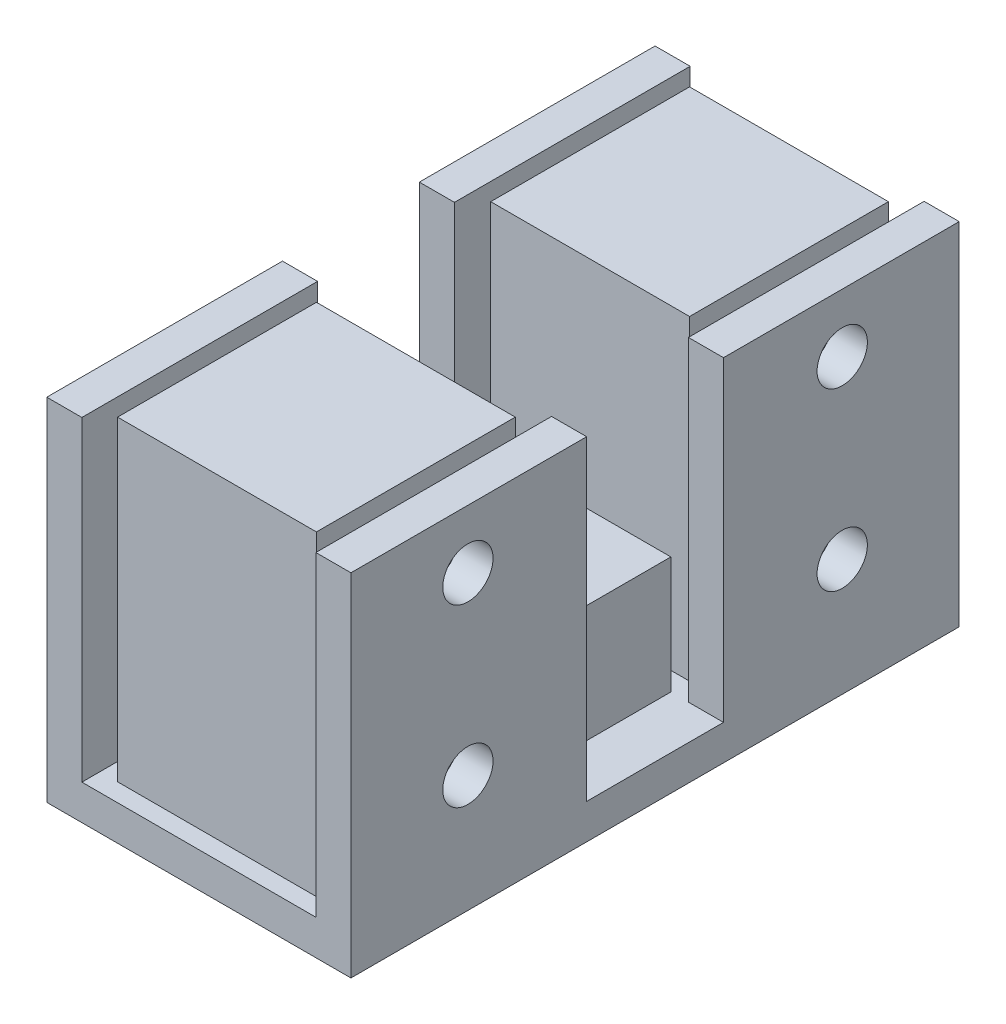
SolidWorks part; units mm, degrees
ref_plane "Front Plane" through (0, 0, 0) normal (0, 0, 1) x (1, 0, 0)
ref_plane "Top Plane" through (0, 0, 0) normal (0, 1, 0) x (1, 0, 0)
ref_plane "Right Plane" through (0, 0, 0) normal (1, 0, 0) x (0, 0, -1)
sketch "Sketch1" plane through (0, 0, 0) normal (0, 1, 0) x (1, 0, 0)
  line L1 (0, 0) -> (26, 0)
  line L2 (0, 0) -> (0, 52)
  line L3 (0, 52) -> (26, 52)
  line L4 (26, 0) -> (26, 52)
  dimension "D1" = 52
  dimension "D2" = 26
extrude "Boss-Extrude1" add sketch "Sketch1" along normal blind 30
sketch "Sketch2" plane through (0, 0, -52) normal (0, 0, -1) x (-1, 0, 0)
  line L0 (-26, 30) -> (0, 30) construction
  line L1 (-23, 30) -> (-21.5, 30)
  line L2 (-23, 30) -> (-23, 3)
  line L3 (-23, 3) -> (-21.5, 3)
  line L4 (-21.5, 30) -> (-21.5, 3)
  line L5 (-26, 30) -> (-26, 0) construction
  line L6 (-4.5, 30) -> (-3, 30)
  line L7 (-4.5, 30) -> (-4.5, 3)
  line L8 (-4.5, 3) -> (-3, 3)
  line L9 (-3, 30) -> (-3, 3)
  line L10 (0, 30) -> (0, 0) construction
  line L11 (-26, 0) -> (0, 0) construction
  dimension "D1" = 17
  dimension "D2" = 3
  dimension "D3" = 3
  dimension "D4" = 3
extrude "Cut-Extrude1" cut sketch "Sketch2" against normal through all
sketch "Sketch3" plane through (0, 30, 0) normal (0, 1, 0) x (1, 0, 0)
  line L0 (4.5, 31.85) -> (4.5, 20.15)
  line L2 (4.5, 50.45) -> (4.5, 33.45)
  line L4 (21.5, 50.45) -> (21.5, 33.45)
  line L5 (4.5, 50.45) -> (21.5, 50.45)
  line L6 (4.5, 50.45) -> (4.5, 33.45)
  line L7 (4.5, 33.45) -> (21.5, 33.45)
  line L8 (21.5, 50.45) -> (21.5, 33.45)
  line L9 (4.5, 18.55) -> (21.5, 18.55)
  line L10 (4.5, 18.55) -> (4.5, 1.55)
  line L11 (4.5, 1.55) -> (21.5, 1.55)
  line L12 (21.5, 18.55) -> (21.5, 1.55)
  line L13 (4.5, 31.85) -> (21.5, 31.85)
  line L14 (4.5, 31.85) -> (4.5, 20.15)
  line L15 (4.5, 20.15) -> (21.5, 20.15)
  line L16 (21.5, 31.85) -> (21.5, 20.15)
  line L17 (21.5, 31.85) -> (21.5, 20.15)
  line L18 (4.5, 18.55) -> (4.5, 1.55)
  line L19 (21.5, 18.55) -> (21.5, 1.55)
  line L20 (21.5, 52) -> (4.5, 52) construction
  line L21 (4.5, 0) -> (4.5, 52) construction
  line L22 (21.5, 0) -> (21.5, 52) construction
  line L23 (4.5, 0) -> (21.5, 0) construction
  line L24 (3, 0) -> (3, 52) construction
  line L25 (0, 52) -> (3, 52)
  line L26 (0, 52) -> (0, 31.85)
  line L27 (0, 31.85) -> (3, 31.85)
  line L28 (3, 52) -> (3, 31.85)
  line L29 (23, 0) -> (23, 52) construction
  line L30 (26, 52) -> (23, 52)
  line L31 (26, 52) -> (26, 31.85)
  line L32 (26, 31.85) -> (23, 31.85)
  line L33 (23, 52) -> (23, 31.85)
  line L35 (0, 0) -> (3, 0)
  line L36 (0, 0) -> (0, 20.15)
  line L37 (0, 20.15) -> (3, 20.15)
  line L38 (3, 0) -> (3, 20.15)
  line L39 (23, 20.15) -> (26, 20.15)
  line L40 (23, 20.15) -> (23, 0)
  line L41 (23, 0) -> (26, 0)
  line L42 (26, 20.15) -> (26, 0)
  line M18 (21.5, 0) -> (21.5, 52)
  line M20 (4.5, 52) -> (4.5, 0)
  dimension "D1" = 17
  dimension "D2" = 17
  dimension "D3" = 1.55
  dimension "D4" = 1.55
  dimension "D5" = 1.6
  dimension "D6" = 1.6
extrude "Cut-Extrude2" cut sketch "Sketch3" against normal up to surface (27 mm away) flip side to cut contours L7 L5 M20 M18 | L15 L13 M20 M18 | L11 L9 M20 M18 | L26 L25 L28 L27 | L31 L30 L33 L32 | L36 L35 L38 L37 | L40 L39 L42 L41 region at (13, 30, -26) region at (13, 30, -41.95) region at (13, 30, -10.05) up to face at (3.75, 3, -26)
sketch "Sketch4" plane through (0, 30, 0) normal (0, 1, 0) x (1, 0, 0)
  line L4 (4.5, 20.15) -> (21.5, 20.15)
  line L5 (21.5, 20.15) -> (21.5, 31.85)
  line L6 (21.5, 31.85) -> (4.5, 31.85)
  line L7 (4.5, 31.85) -> (4.5, 20.15)
  line L8 (4.5, 20.15) -> (21.5, 20.15)
  line L9 (21.5, 20.15) -> (21.5, 31.85)
  line L10 (21.5, 31.85) -> (4.5, 31.85)
  line L11 (4.5, 31.85) -> (4.5, 20.15)
  dimension "D1" = 0
extrude "Cut-Extrude3" cut sketch "Sketch4" against normal offset from surface (17 mm away) 10 up to face at (13, 3, -10.05)
sketch "Sketch5" plane through (0, 0, 0) normal (-1, 0, 0) x (0, 0, 1)
  line L0 (-52, 30) -> (-52, 0) construction
  line L1 (-52, 30) -> (-31.85, 30) construction
  line L2 (0, 30) -> (0, 0) construction
  circle A0 centre (-42, 25) radius 2.15
  circle A1 centre (-42, 10) radius 2.15
  circle A2 centre (-10, 25) radius 2.15
  circle A3 centre (-10, 10) radius 2.15
  point P8 (0, 0)
  point P9 (0, 0)
  point P14 (0, 0)
  point P17 (-10, 12.2009)
  point P18 (-10, 21.706)
  point P19 (0, 0)
  dimension "D1" = 4.3
  dimension "D2" = 10
  dimension "D3" = 15
  dimension "D4" = 5
  dimension "D5" = 10
extrude "Cut-Extrude4" cut sketch "Sketch5" against normal through all
